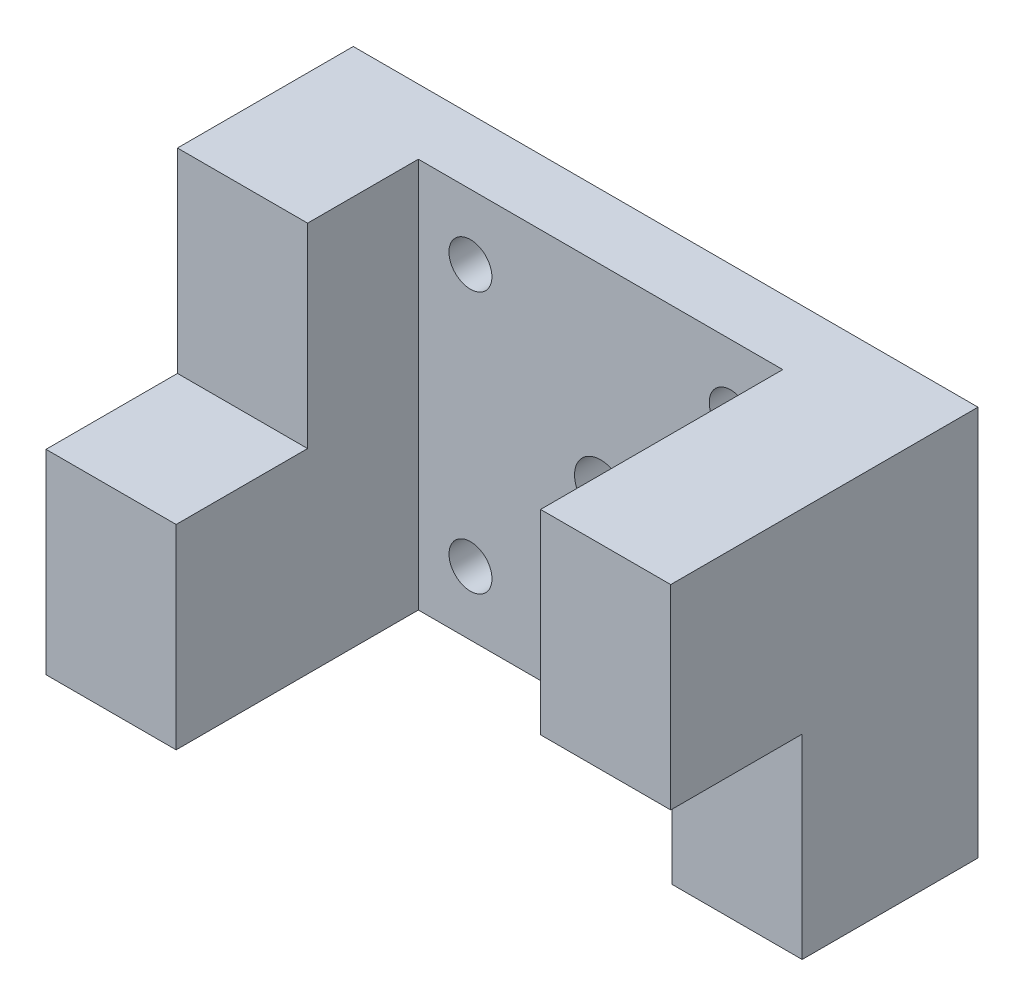
SolidWorks part; units mm, degrees
ref_plane "Front Plane" through (0, 0, 0) normal (0, 0, 1) x (1, 0, 0)
ref_plane "Top Plane" through (0, 0, 0) normal (0, 1, 0) x (1, 0, 0)
ref_plane "Right Plane" through (0, 0, 0) normal (1, 0, 0) x (0, 0, -1)
sketch "Sketch1" plane through (0, 0, 0) normal (0, 0, 1) x (1, 0, 0)
  line L1 (-10, -10) -> (10, -10) construction
  line L2 (-10, -10) -> (-10, 10) construction
  line L3 (-10, 10) -> (10, 10) construction
  line L4 (10, -10) -> (10, 10) construction
  line L5 (-10, -10) -> (10, 10) construction
  line L6 (-10, 10) -> (10, -10) construction
  line L7 (-24, -15) -> (24, -15)
  line L8 (-24, -15) -> (-24, 15)
  line L9 (-24, 15) -> (24, 15)
  line L10 (24, -15) -> (24, 15)
  line L11 (-24, -15) -> (24, 15) construction
  line L12 (-24, 15) -> (24, -15) construction
  circle A0 centre (-10, 10) radius 1.65
  circle A1 centre (10, 10) radius 1.65
  circle A2 centre (10, -10) radius 1.65
  circle A3 centre (-9.9952, -10.0965) radius 1.65
  circle A4 centre (0, 0) radius 2
  point P0 (0, 0)
  dimension "D2" = 3.3
  dimension "D3" = 4
  dimension "D1" = 20
  dimension "D4" = 30
  dimension "D5" = 48
extrude "Boss-Extrude1" add sketch "Sketch1" along normal blind 5
sketch "Sketch2" plane through (0, 0, 5) normal (0, 0, 1) x (1, 0, 0)
  line L1 (-24, 15) -> (-14, 15)
  line L2 (-24, 15) -> (-24, -15)
  line L3 (-24, -15) -> (-14, -15)
  line L4 (-14, 15) -> (-14, -15)
  line L5 (-24, -15) -> (24, -15) construction
  line L7 (24, 15) -> (14, 15)
  line L8 (24, 15) -> (24, -15)
  line L9 (24, -15) -> (14, -15)
  line L10 (14, 15) -> (14, -15)
  line L11 (-14, -15) -> (-24, -15)
  line L12 (-14, -15) -> (-14, 0)
  line L13 (-14, 0) -> (-24, 0)
  line L14 (-24, -15) -> (-24, 0)
  line L15 (14, -15) -> (24, -15)
  line L16 (14, -15) -> (14, 0)
  line L17 (14, 0) -> (24, 0)
  line L18 (24, -15) -> (24, 0)
  line M1 (24, -15) -> (24, 15)
  line M2 (24, 15) -> (-24, 15)
  line M3 (-24, 15) -> (-24, -15)
  line M4 (-24, -15) -> (24, -15)
  dimension "D1" = 30
  dimension "D2" = 10
  dimension "D3" = 30
  dimension "D4" = 10
  dimension "D5" = 15
  dimension "D6" = 10
  dimension "D7" = 15
  dimension "D8" = 10
extrude "Boss-Extrude2" add sketch "Sketch2" along normal blind 18.61 contours L10 L17 L8 M2 | L4 L13 L2 M4 region at (-19, -7.5, 5) region at (19, 7.5, 5)
extrude "Boss-Extrude3" add sketch "Sketch2<3>" along normal blind 8.51 contours L17 L10 M4 M1 | L13 L4 M2 M3 region at (-19, 7.5, 5) region at (19, -7.5, 5)
sketch "Sketch2<3>" plane through (0, 0, 5) normal (0, 0, 1) x (1, 0, 0) same geometry as "Sketch2"
